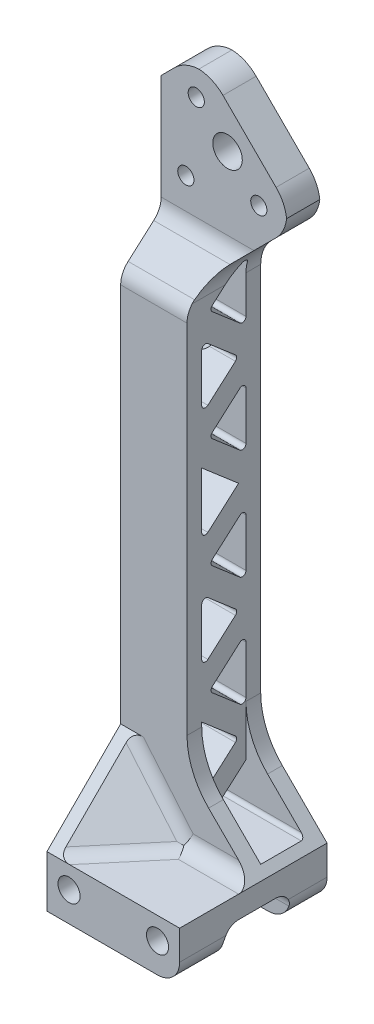
SolidWorks part; units mm, degrees
ref_plane "Front Plane" through (0, 0, 0) normal (0, 0, 1) x (1, 0, 0)
ref_plane "Top Plane" through (0, 0, 0) normal (0, 1, 0) x (1, 0, 0)
ref_plane "Right Plane" through (0, 0, 0) normal (1, 0, 0) x (0, 0, -1)
sketch "Sketch2" plane through (0, 0, 0) normal (0, 0, 1) x (1, 0, 0)
  line L0 (0, 90.435) -> (0, 0)
  line L1 (0, 0) -> (15, 0)
  line L2 (18, 3) -> (18, 7)
  line L3 (18, 7) -> (11.9289, 13.0711)
  line L4 (9, 20.1421) -> (9, 72.565)
  line L5 (9, 72.565) -> (9, 86) construction
  line L6 (3, 4) -> (15, 4) construction
  line L7 (0, 90.435) -> (3.3076, 93.7426)
  line L8 (3.3076, 93.7426) -> (6.9142, 93.7426)
  line L9 (6.9142, 93.7426) -> (17.0459, 83.6109)
  line L10 (17.0459, 83.6109) -> (17.0459, 80.6109)
  line L11 (17.0459, 80.6109) -> (9, 72.565)
  line L12 (9, 86) -> (13.2426, 81.7574) construction
  line L13 (3.3431, 80.3431) -> (9, 86) construction
  line L14 (9, 86) -> (4.7574, 90.2426) construction
  circle A0 centre (9, 86) radius 6 construction
  circle A1 centre (9, 86) radius 8 construction
  circle A2 centre (15, 4) radius 1.5
  circle A3 centre (3, 4) radius 1.5
  arc A4 (15, 0) -> (18, 3) centre (15, 3) ccw
  circle A5 centre (13.2426, 81.7574) radius 1.1
  circle A6 centre (3.3431, 80.3431) radius 1.1
  circle A7 centre (4.7574, 90.2426) radius 1.1
  circle A8 centre (9, 86) radius 2
  arc A9 (11.9289, 13.0711) -> (9, 20.1421) centre (19, 20.1421) cw
  dimension "D6" = 3
  dimension "D9" = 3
  dimension "D11" = 16
  dimension "D12" = 12
  dimension "D16" = 2.2
  dimension "D21" = 4
  dimension "D24" = 10
  dimension "D1" = 18
  dimension "D2" = 7
  dimension "D3" = 12
  dimension "D4" = 4
  dimension "D5" = 3
  dimension "D7" = 45
  dimension "D8" = 9
  dimension "D10" = 82
  dimension "D13" = 45
  dimension "D14" = 90
  dimension "D15" = 90
  dimension "D17" = 3.5
  dimension "D18" = 45
  dimension "D19" = 3.5
  dimension "D20" = 3.5
  dimension "D22" = 3
  dimension "D23" = 4
extrude "Boss-Extrude2" add sketch "Sketch2" along normal blind 10
sketch "Sketch3" plane through (0, 0, 0) normal (-1, 0, 0) x (0, 0, 1)
  line L0 (2, -2.1921) -> (2, 96.2523) construction
  line L1 (2, 96.2523) -> (3, 96.2523) construction
  line L2 (3, 96.2523) -> (3, -2.1921) construction
  line L3 (3, -2.1921) -> (5, -2.1921) construction
  line L4 (5, -2.1921) -> (5, 96.2523) construction
  line L5 (5, 96.2523) -> (7, 96.2523) construction
  line L6 (7, 96.2523) -> (7, -2.1921) construction
  line L7 (7, -2.1921) -> (8, -2.1921) construction
  line L8 (8, -2.1921) -> (8, 96.2523) construction
  line L9 (10, 90.435) -> (10, 0) construction
  line L10 (10, 0) -> (0, 0) construction
  line L11 (2, 8) -> (8, 8)
  line L12 (8, 8) -> (2, 13.3)
  line L13 (2, 13.3) -> (2, 8)
  line L14 (8, 20.7122) -> (8, 12.0028)
  line L15 (8, 12.0028) -> (3, 16.4195)
  line L16 (3, 16.4195) -> (8, 20.7122)
  line L17 (2, 28.2243) -> (2, 19.5149)
  line L18 (2, 19.5149) -> (7, 23.8076)
  line L19 (7, 23.8076) -> (2, 28.2243)
  line L20 (2, 43.1486) -> (2, 34.4392)
  line L21 (2, 34.4392) -> (7, 38.7319)
  line L22 (7, 38.7319) -> (2, 43.1486)
  line L23 (2, 58.0729) -> (2, 49.3635)
  line L24 (2, 49.3635) -> (7, 53.6562)
  line L25 (7, 53.6562) -> (2, 58.0729)
  line L26 (2, 72.9972) -> (2, 64.2878)
  line L27 (2, 64.2878) -> (7, 68.5805)
  line L28 (7, 68.5805) -> (2, 72.9972)
  line L29 (8, 35.6365) -> (8, 26.9271)
  line L30 (8, 26.9271) -> (3, 31.3438)
  line L31 (3, 31.3438) -> (8, 35.6365)
  line L32 (8, 50.5608) -> (8, 41.8514)
  line L33 (8, 41.8514) -> (3, 46.2681)
  line L34 (3, 46.2681) -> (8, 50.5608)
  line L35 (8, 65.4851) -> (8, 56.7757)
  line L36 (8, 56.7757) -> (3, 61.1924)
  line L37 (3, 61.1924) -> (8, 65.4851)
  line L38 (10, 0) -> (0, 0) construction
  line L43 (0, 90.435) -> (0, 0) construction
  line L44 (2, 77) -> (8, 77)
  line L45 (8, 77) -> (8, 71.7)
  line L46 (8, 71.7) -> (2, 77)
  dimension "D1" = 2
  dimension "D2" = 2
  dimension "D3" = 1
  dimension "D4" = 1
  dimension "D5" = 2
  dimension "D6" = 5.3
  dimension "D7" = 3
  dimension "D8" = 77
  dimension "D11" = 8
  dimension "D12" = 2
  dimension "D13" = 3
  dimension "D14" = 3
  dimension "D15" = 3
  dimension "D16" = 3
  dimension "D9" = 4
  dimension "D10" = 4
extrude "Cut-Extrude1" cut sketch "Sketch3" against normal up to next
sketch "Sketch5" plane through (9, 0, 0) normal (1, 0, 0) x (0, 0, -1)
  line L0 (-2, 8) -> (-8, 8)
  line L1 (-8, 8) -> (-8, 21.7117)
  line L2 (-8, 21.7117) -> (-2, 21.7117)
  line L3 (-2, 28.2243) -> (-2, 19.5149) construction
  line L4 (-2, 21.7117) -> (-2, 8)
extrude "Cut-Extrude2" cut sketch "Sketch5" along normal blind 30
fillet "Fillet3" radius 0.5 1 edges at (4.5, 16.4195, 3)
fillet "Fillet4" radius 0.5 1 edges at (4.5, 28.2243, 2)
fillet "Fillet5" radius 0.5 1 edges at (4.5, 19.5149, 2)
fillet "Fillet6" radius 0.5 1 edges at (4.5, 35.6365, 8)
fillet "Fillet7" radius 0.5 1 edges at (4.5, 53.6562, 7)
fillet "Fillet8" radius 0.5 1 edges at (8.5, 8, 2)
fillet "Fillet9" radius 0.5 1 edges at (4.5, 65.4851, 8)
fillet "Fillet10" radius 0.5 1 edges at (4.7161, 72.9972, 2)
fillet "Fillet11" radius 0.5 1 edges at (4.5, 31.3438, 3)
fillet "Fillet12" radius 0.5 1 edges at (4.5, 61.1924, 3)
fillet "Fillet13" radius 0.5 1 edges at (4.5, 26.9271, 8)
fillet "Fillet14" radius 0.5 1 edges at (4.5, 58.0729, 2)
fillet "Fillet15" radius 0.5 1 edges at (4.5, 71.7, 8)
fillet "Fillet16" radius 0.5 1 edges at (4.5, 43.1486, 2)
fillet "Fillet17" radius 0.5 1 edges at (4.5, 12.0028, 8)
fillet "Fillet18" radius 0.5 1 edges at (4.5, 23.8076, 7)
fillet "Fillet19" radius 0.5 1 edges at (4.5, 56.7757, 8)
fillet "Fillet20" radius 0.5 1 edges at (4.5, 41.8514, 8)
fillet "Fillet21" radius 0.5 1 edges at (4.5, 68.5805, 7)
fillet "Fillet22" radius 0.5 1 edges at (4.5, 64.2878, 2)
fillet "Fillet23" radius 0.5 1 edges at (4.5, 38.7319, 7)
fillet "Fillet24" radius 0.5 1 edges at (4.5, 34.4392, 2)
fillet "Fillet25" radius 0.5 1 edges at (6.7175, 77, 8)
fillet "Fillet26" radius 0.5 1 edges at (6.7175, 77, 2)
fillet "Fillet27" radius 0.5 1 edges at (4.5, 49.3635, 2)
sketch "Sketch6" plane through (0, 0, 10) normal (0, 0, 1) x (1, 0, 0)
  line L0 (18, 7) -> (0, 7)
  line L1 (0, 90.435) -> (0, 0) construction
  line L2 (0, 0) -> (15, 0) construction
  line L3 (18, 3) -> (18, 7) construction
  line L4 (0, 90.435) -> (0, 0)
  line L5 (0, 0) -> (15, 0)
  line L6 (18, 3) -> (18, 7)
  line L7 (0, 7) -> (0, 0)
  arc A0 (15, 0) -> (18, 3) centre (15, 3) ccw construction
  arc A1 (15, 0) -> (18, 3) centre (15, 3) ccw
  line M2 (0, 90.435) -> (0, 0)
  line M3 (0, 0) -> (15, 0)
  arc M4 (15, 0) -> (18, 3) centre (15, 3) ccw
  line M5 (18, 3) -> (18, 7)
  circle M13 centre (15, 4) radius 1.5
  circle M14 centre (3, 4) radius 1.5
extrude "Boss-Extrude3" add sketch "Sketch6" along normal blind 10 contours L0 M5 M2 M3 M4 M14 M13 region at (8.8536, 3.4854, 10)
sketch "Sketch7" plane through (0, 0, 0) normal (-1, 0, 0) x (0, 0, 1)
  line L0 (20, 0) -> (0, 0) construction
  line L1 (14, 0) -> (5, 0)
  line L2 (14, 0) -> (14, 4)
  line L3 (14, 4) -> (5, 4)
  line L4 (5, 0) -> (5, 4)
  line L5 (0, 90.435) -> (0, 0) construction
  line L6 (20, 7) -> (20, 0) construction
  dimension "D1" = 5
  dimension "D2" = 6
  dimension "D3" = 4
extrude "Cut-Extrude3" cut sketch "Sketch7" against normal through all
sketch "Sketch8" plane through (0, 0, 0) normal (-1, 0, 0) x (0, 0, 1)
  line L0 (10, 7) -> (20, 7)
  line L1 (20, 7) -> (10, 17)
  line L2 (10, 90.435) -> (10, 7) construction
  line L3 (10, 17) -> (10, 7)
  dimension "D1" = 45
extrude "Boss-Extrude4" add sketch "Sketch8" against normal blind 10
sketch "Sketch12" plane through (0, 0, 0) normal (-1, 0, 0) x (0, 0, 1)
  line L0 (7.5, 77) -> (3.3213, 77) construction
  line L1 (8, 72.8088) -> (8, 76.5) construction
  line L2 (2.9903, 76.1253) -> (7.169, 72.4341) construction
  line L3 (7.5, 77) -> (3.3213, 77)
  line L4 (8, 72.8088) -> (8, 76.5)
  line L5 (2.9903, 76.1253) -> (7.169, 72.4341)
  arc A0 (3.3213, 77) -> (2.9903, 76.1253) centre (3.3213, 76.5) ccw construction
  arc A1 (8, 76.5) -> (7.5, 77) centre (7.5, 76.5) ccw construction
  arc A2 (7.169, 72.4341) -> (8, 72.8088) centre (7.5, 72.8088) ccw construction
  arc A3 (3.3213, 77) -> (2.9903, 76.1253) centre (3.3213, 76.5) ccw
  arc A4 (8, 76.5) -> (7.5, 77) centre (7.5, 76.5) ccw
  arc A5 (7.169, 72.4341) -> (8, 72.8088) centre (7.5, 72.8088) ccw
extrude "Boss-Extrude5" add sketch "Sketch12" against normal up to surface (9.2438 mm away) up to face at (11.9923, 75.5572, 5.8714)
sketch "Sketch13" plane through (0, 0, 0) normal (-1, 0, 0) x (0, 0, 1)
  line L0 (10, 69.9333) -> (10, 99.9736)
  line L1 (10, 90.435) -> (10, 17) construction
  line L2 (10, 99.9736) -> (4.5, 99.9736)
  line L3 (4.5, 99.9736) -> (4.5, 74.7917)
  line L4 (4.5, 74.7917) -> (10, 69.9333)
  line L5 (6.5697, 68.9606) -> (2.831, 72.2631) construction
  line L6 (0, 90.435) -> (0, 0) construction
  point P10 (4.5, 87.3826)
  dimension "D1" = 3
  dimension "D2" = 4.5
extrude "Cut-Extrude4" cut sketch "Sketch13" against normal through all
fillet "Fillet29" radius 2 2 edges at (9, 4, 5) (9, 4, 14)
chamfer "Chamfer1" distance 7 angle 50 1 edges at (10, 12, 15) first distance on face at (10, 11.6958, 12.5)
fillet "Fillet30" radius 2 3 edges at (14, 7, 10) (5.8289, 12.0503, 10) (5.8289, 7, 15.0503)
fillet "Fillet31" radius 3 2 edges at (4.5, 69.9333, 10) (5.6133, 74.7917, 4.5)
fillet "Fillet32" radius 5 5 edges at (9, 72.565, 3.5104) (17.0459, 80.6109, 2.25) (17.0459, 83.6109, 2.25) (6.9142, 93.7426, 2.25) (3.3076, 93.7426, 2.25)
sketch "Sketch14" plane through (0, 0, 0) normal (0, 0, -1) x (-1, 0, 0)
  line L0 (0, 90.435) -> (0, 0) construction
  circle A0 centre (-4.5, 61.5913) radius 1.25
  dimension "D2" = 2.5
  dimension "D1" = 4.5
  dimension "D3" = 32.15
extrude "Cut-Extrude5" cut sketch "Sketch14" against normal blind 6
